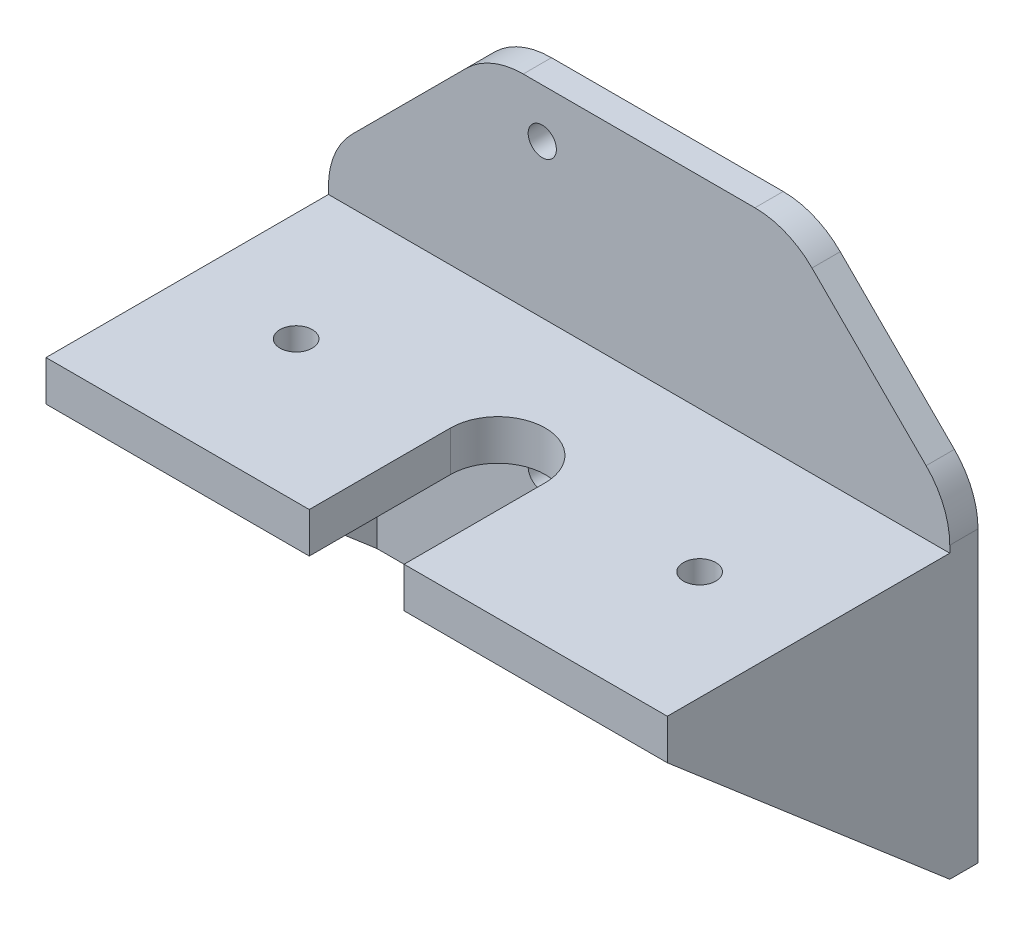
SolidWorks part; units mm, degrees
ref_plane "Front Plane" through (0, 0, 0) normal (0, 0, 1) x (1, 0, 0)
ref_plane "Top Plane" through (0, 0, 0) normal (0, 1, 0) x (1, 0, 0)
ref_plane "Right Plane" through (0, 0, 0) normal (1, 0, 0) x (0, 0, -1)
sketch "Sketch1" plane through (0, 0, 0) normal (0, 0, 1) x (1, 0, 0)
  line L1 (-50.5, 41.85) -> (26.5, 41.85)
  line L2 (-50.5, 41.85) -> (-50.5, -18.15)
  line L3 (-50.5, -18.15) -> (26.5, -18.15)
  line L4 (26.5, 41.85) -> (26.5, -18.15)
  circle A0 centre (-24, 35.8) radius 1.75
  circle A1 centre (-24, 0) radius 1.75
  circle A2 centre (0, 0) radius 1.75
  dimension "D1" = 35.8
  dimension "D2" = 3.5
  dimension "D3" = 24
  dimension "D4" = 77
  dimension "D5" = 26.5
  dimension "D6" = 60
  dimension "D7" = 18.15
extrude "Boss-Extrude1" add sketch "Sketch1" along normal blind 3.5
sketch "Sketch2" plane through (0, 0, 3.5) normal (0, 0, 1) x (1, 0, 0)
  line L0 (-50.5, 41.85) -> (-50.5, -18.15) construction
  line L1 (-50.5, 16.85) -> (26.5, 16.85)
  line L2 (-50.5, 16.85) -> (-50.5, 11.85)
  line L3 (-50.5, 11.85) -> (26.5, 11.85)
  line L4 (26.5, 16.85) -> (26.5, 11.85)
  line L5 (26.5, -18.15) -> (26.5, 41.85) construction
  line L6 (-50.5, -18.15) -> (26.5, -18.15) construction
  dimension "D1" = 5
  dimension "D2" = 30
extrude "Boss-Extrude2" add sketch "Sketch2" along normal blind 35
sketch "Sketch3" plane through (0, 16.85, 0) normal (0, 1, 0) x (1, 0, 0)
  line L0 (-12, -38.5) -> (-12, -3.5) construction
  line L1 (26.5, -38.5) -> (-50.5, -38.5) construction
  line L2 (26.5, -3.5) -> (-50.5, -3.5) construction
  line L3 (-17.875, -21) -> (-17.875, -38.5)
  line L4 (-6.125, -21) -> (-6.125, -38.5)
  line L5 (-6.125, -38.5) -> (-17.875, -38.5)
  arc A0 (-6.125, -21) -> (-17.875, -21) centre (-12, -21) ccw
  dimension "D1" = 11.75
extrude "Cut-Extrude1" cut sketch "Sketch3" against normal blind 20
sketch "Sketch4" plane through (0, 16.85, 0) normal (0, 1, 0) x (1, 0, 0)
  line L0 (26.5, -21) -> (-50.5, -21) construction
  line L1 (26.5, -38.5) -> (26.5, -3.5) construction
  line L2 (-50.5, -38.5) -> (-50.5, -3.5) construction
  circle A0 centre (13, -21) radius 2
  circle A1 centre (-37, -21) radius 2
  dimension "D1" = 4
  dimension "D2" = 50
  dimension "D3" = 13.5
extrude "Cut-Extrude2" cut sketch "Sketch4" against normal blind 20
sketch "Sketch5" plane through (26.5, 0, 0) normal (1, 0, 0) x (0, 0, -1)
  line L0 (-38.5, 11.85) -> (-3.5, -18.15)
rib "Rib2" sketch "Sketch5" sketch "Sketch5" thickness 6 extrusion direction parallel to sketch draft on no parameters "D1"=6
ref_plane "Plane1" through (-12, 0, 0) normal (1, 0, 0) x (0, 0, -1)
mirror "Mirror1" about plane through (-12, 0, 0) normal (1, 0, 0) of "Rib2"
chamfer "Chamfer1" distance 20 angle 45 2 edges at (-50.5, 41.85, 1.75) (26.5, 41.85, 1.75)
fillet "Fillet1" radius 10 4 edges at (-50.5, 21.85, 1.75) (-30.5, 41.85, 1.75) (26.5, 21.85, 1.75) (6.5, 41.85, 1.75)
equation "\"D5@Sketch1\"=(\"D4@Sketch1\"-\"D3@Sketch1\")/2"
equation "\"D7@Sketch1\"=3*(\"D6@Sketch1\"-\"D1@Sketch1\")/4"
equation "\"D3@Sketch4\"=(77-50)/2"
